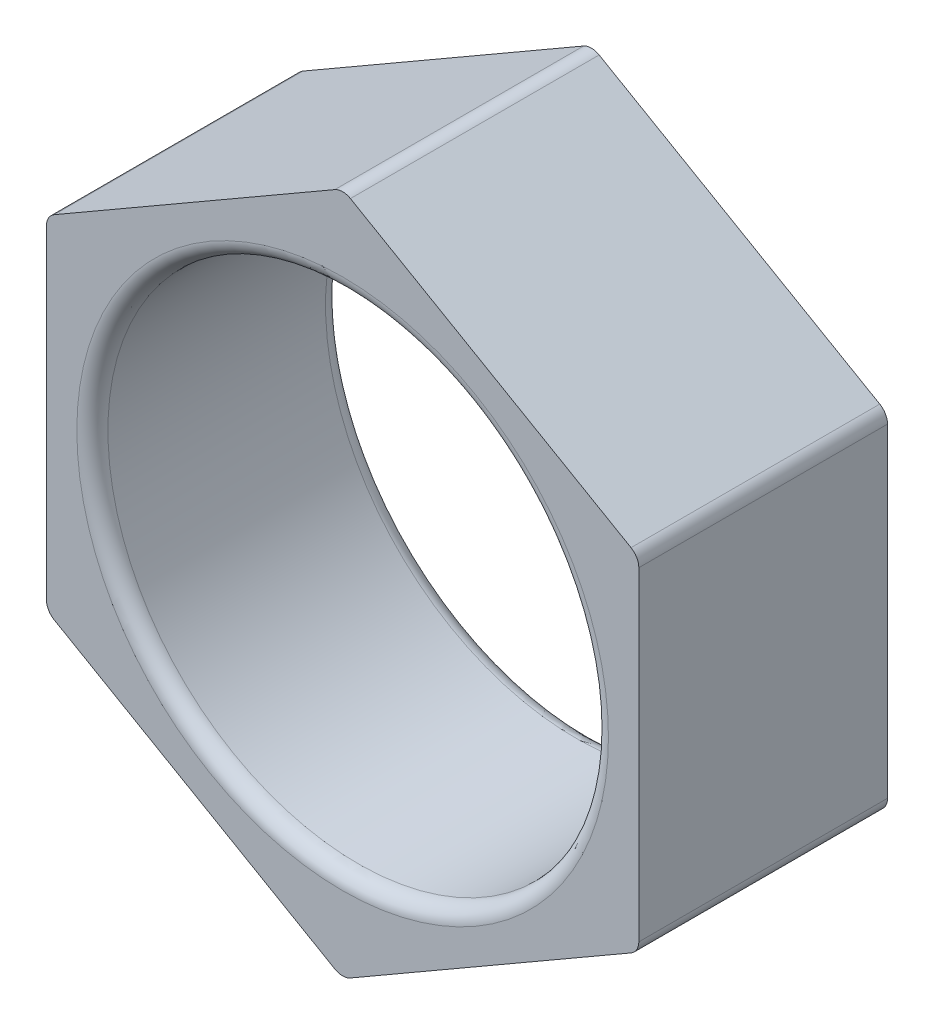
SolidWorks part; units mm, degrees
ref_plane "Front Plane" through (0, 0, 0) normal (0, 0, 1) x (1, 0, 0)
ref_plane "Top Plane" through (0, 0, 0) normal (0, 1, 0) x (1, 0, 0)
ref_plane "Right Plane" through (0, 0, 0) normal (1, 0, 0) x (0, 0, -1)
sketch "Sketch1" plane through (0, 0, 0) normal (0, 0, 1) x (1, 0, 0)
  line L1 (0, 5.5) -> (-4.7631, 2.75)
  line L2 (-4.7631, 2.75) -> (-4.7631, -2.75)
  line L3 (-4.7631, -2.75) -> (0, -5.5)
  line L4 (0, -5.5) -> (4.7631, -2.75)
  line L5 (4.7631, -2.75) -> (4.7631, 2.75)
  line L6 (4.7631, 2.75) -> (0, 5.5)
  circle A0 centre (0, 0) radius 4.7631 construction
  dimension "D1" = 11
extrude "Boss-Extrude1" add sketch "Sketch1" along normal blind 4
sketch "Sketch2" plane through (0, 0, 4) normal (0, 0, 1) x (1, 0, 0)
  circle A0 centre (0, 0) radius 4.025
  dimension "D1" = 8.05
extrude "Cut-Extrude1" cut sketch "Sketch2" against normal through all
fillet "Fillet1" radius 0.25 8 edges at (4.025, 0, 4) (4.025, 0, 0) (-4.7631, 2.75, 2) (-4.7631, -2.75, 2) (0, -5.5, 2) (4.7631, -2.75, 2) (4.7631, 2.75, 2) (0, 5.5, 2)
